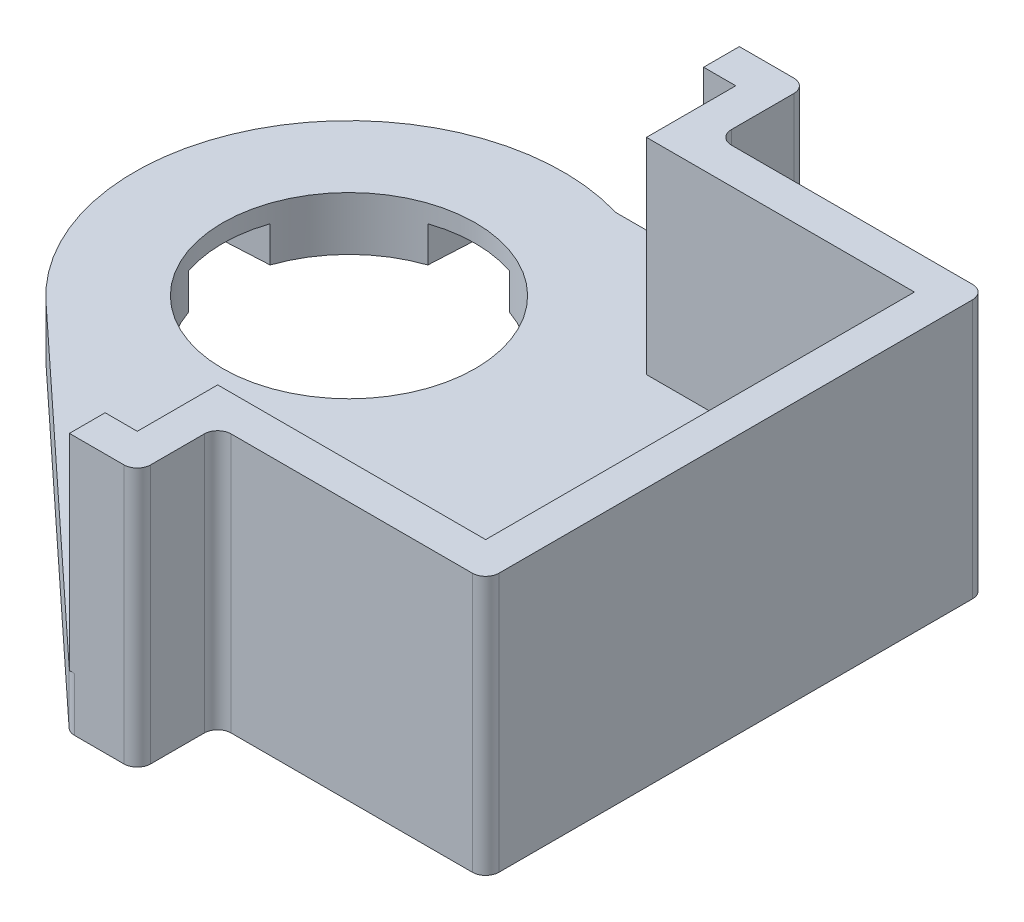
SolidWorks part; units mm, degrees
ref_plane "Front Plane" through (0, 0, 0) normal (0, 0, 1) x (1, 0, 0)
ref_plane "Top Plane" through (0, 0, 0) normal (0, 1, 0) x (1, 0, 0)
ref_plane "Right Plane" through (0, 0, 0) normal (1, 0, 0) x (0, 0, -1)
sketch "Sketch1" plane through (0, 0, 0) normal (0, 1, 0) x (1, 0, 0)
  line L0 (3.35, 28) -> (3.35, 23)
  line L9 (0, 0) -> (3.35, 0)
  line L10 (0, 0) -> (0, 23)
  line L11 (0, 23) -> (3.35, 23)
  line L12 (19.65, 0) -> (19.65, 23)
  line L14 (4.65, 0) -> (4.65, -5)
  line L15 (4.65, -5) -> (3.35, -5)
  line L16 (3.35, 0) -> (3.35, -5)
  line L17 (4.65, -5) -> (3.35, -5)
  line L18 (4.65, -5) -> (4.65, 28) construction
  line L19 (4.65, 28) -> (3.35, 28)
  line L20 (3.35, -5) -> (3.35, 28) construction
  line L21 (4.65, 28) -> (4.65, 23)
  line L22 (4.65, 0) -> (19.65, 0)
  line L23 (4.65, 23) -> (19.65, 23)
  line L24 (2.85, 28) -> (2.85, 23.5)
  line L25 (-0.5, 23.5) -> (2.85, 23.5)
  line L26 (-0.5, -0.5) -> (-0.5, 23.5)
  line L27 (-0.5, -0.5) -> (2.85, -0.5)
  line L28 (2.85, -0.5) -> (2.85, -5)
  line L29 (5.15, -0.5) -> (5.15, -5)
  line L30 (5.15, -0.5) -> (20.15, -0.5)
  line L31 (20.15, -0.5) -> (20.15, 23.5)
  line L32 (5.15, 23.5) -> (20.15, 23.5)
  line L33 (5.15, 28) -> (5.15, 23.5)
  line L34 (4.65, -4.5) -> (3.35, -4.5)
  line L35 (4.65, -4.5) -> (3.35, -4.5)
  line L37 (5.15, -5) -> (5.15, 28)
  line L38 (3.85, -5) -> (3.85, 28)
  line L39 (2.85, -5) -> (3.35, -5)
  line L40 (5.15, -5) -> (4.65, -5)
  line L41 (3.35, 28) -> (5.15, 28)
  line L42 (4.65, 28) -> (3.35, 28)
  line L43 (5.15, 28) -> (5.15, 28.5)
  line L46 (2.85, 28) -> (2.85, 28.5)
  line L47 (2.85, 28.5) -> (5.15, 28.5)
  line L48 (5.15, 28) -> (5.15, 28.5)
  dimension "D1" = 23
  dimension "D2" = 19.65
  dimension "D3" = 15
  dimension "D4" = 1.3
  dimension "D5" = 5
  dimension "D6" = 5
  dimension "D7" = 0.5
sketch "Sketch3" plane through (0, 0, 0) normal (0, 1, 0) x (1, 0, 0)
  line L1 (3.35, -5) -> (7.15, -5)
  line L2 (3.35, -5) -> (3.35, 28)
  line L3 (3.35, 28) -> (7.15, 28)
  line L4 (7.15, -5) -> (7.15, -2.5)
  line L5 (4.65, 28) -> (3.35, 28) construction
  line L6 (7.15, 25.5) -> (7.15, 28)
  line L7 (4.65, -5) -> (3.35, -5) construction
  line L8 (7.15, 25.5) -> (22.15, 25.5)
  line L10 (7.15, -2.5) -> (22.15, -2.5)
  line L11 (22.15, 25.5) -> (22.15, -2.5)
  line L12 (4.65, 23) -> (19.65, 23) construction
  line L13 (19.65, 0) -> (19.65, 23) construction
  line L14 (4.65, 0) -> (19.65, 0) construction
  line L15 (4.65, 0) -> (4.65, -5) construction
  point P20 (7.15, -3.75)
  dimension "D1" = 2.5
  dimension "D2" = 2.5
  dimension "D3" = 2.5
  dimension "D4" = 2.5
sketch "Sketch9" plane through (0, 0, 0) normal (0, 1, 0) x (1, 0, 0)
  line L0 (3.35, 28) -> (3.35, 23)
  line L9 (0, 0) -> (3.35, 0)
  line L10 (0, 0) -> (0, 23)
  line L11 (0, 23) -> (3.35, 23)
  line L12 (19.65, 0) -> (19.65, 23)
  line L14 (4.65, 0) -> (4.65, -4.5)
  line L15 (4.65, -5) -> (3.35, -5)
  line L16 (3.35, 0) -> (3.35, -4.5)
  line L17 (4.65, -5) -> (3.35, -5)
  line L18 (4.65, -4.5) -> (4.65, 28) construction
  line L19 (4.65, 28) -> (3.35, 28)
  line L20 (3.35, -4.5) -> (3.35, 28) construction
  line L21 (4.65, 28) -> (4.65, 23)
  line L22 (4.65, 0) -> (19.65, 0)
  line L23 (4.65, 23) -> (19.65, 23)
  line L24 (4.65, 28) -> (3.35, 28)
  line L25 (5.15, -5) -> (3.35, -5)
  line L26 (7.15, -5) -> (7.15, -6.25)
  line L27 (6.4, -7) -> (3.35, -7)
  line L28 (3.35, -5) -> (3.35, -7)
  line L29 (5.15, -0.5) -> (5.15, -5)
  line L30 (5.15, -0.5) -> (20.15, -0.5)
  line L31 (20.15, -0.5) -> (20.15, 23.5)
  line L32 (5.15, 23.5) -> (20.15, 23.5)
  line L33 (5.15, 28) -> (5.15, 23.5)
  line L34 (4.65, -4.5) -> (3.35, -4.5)
  line L35 (4.65, -4.5) -> (3.35, -4.5)
  line L36 (7.15, 28) -> (7.15, 26.25)
  line L37 (5.15, -5) -> (5.15, -0.5)
  line L38 (3.35, -5) -> (3.35, -7)
  line L40 (5.15, -5) -> (4.65, -5)
  line L41 (3.35, 28) -> (4.65, 28)
  line L42 (4.65, 28) -> (3.35, 28)
  line L43 (5.15, 28) -> (5.15, 28.5)
  line L47 (3.35, 30.5) -> (5.15, 30.5)
  line L48 (5.15, 28) -> (5.15, 28.5)
  line L49 (7.9, 25.5) -> (21.4, 25.5)
  line L50 (22.15, -1.75) -> (22.15, 24.75)
  line L51 (7.9, -2.5) -> (21.4, -2.5)
  line L52 (7.15, -3.25) -> (7.15, -5)
  line L53 (5.15, 23.5) -> (5.15, 28)
  line L54 (7.15, 28) -> (7.15, 29.75)
  line L55 (6.4, 30.5) -> (3.35, 30.5)
  line L57 (5.15, -5) -> (5.15, 28) construction
  line L58 (7.15, -2.5) -> (22.15, -2.5) construction
  line L60 (3.35, 30.5) -> (5.15, 30.5)
  line L61 (3.35, 30.5) -> (3.35, 28.5)
  line L62 (3.35, 28.5) -> (5.15, 28.5)
  line L64 (4.65, 0) -> (4.65, -5) construction
  line L65 (4.65, -5) -> (4.65, 28) construction
  line L66 (7.15, -2.5) -> (7.15, -5) construction
  line L67 (7.15, 28) -> (7.15, 25.5) construction
  line L68 (7.15, 25.5) -> (22.15, 25.5) construction
  line L69 (22.15, -2.5) -> (22.15, 25.5) construction
  arc A0 (7.9, -2.5) -> (7.15, -3.25) centre (7.9, -3.25) ccw
  arc A1 (7.15, 26.25) -> (7.9, 25.5) centre (7.9, 26.25) ccw
  arc A2 (7.15, 29.75) -> (6.4, 30.5) centre (6.4, 29.75) ccw
  arc A3 (21.4, 25.5) -> (22.15, 24.75) centre (21.4, 24.75) cw
  arc A4 (22.15, -1.75) -> (21.4, -2.5) centre (21.4, -1.75) cw
  arc A5 (7.15, -6.25) -> (6.4, -7) centre (6.4, -6.25) cw
  dimension "D10" = 0.75
  dimension "D1" = 23
  dimension "D2" = 19.65
  dimension "D3" = 15
  dimension "D4" = 1.3
  dimension "D5" = 5
  dimension "D6" = 5
  dimension "D7" = 0.5
  dimension "D8" = 2.5
  dimension "D9" = 2
  dimension "D11" = 0.5
extrude "Bracket" add sketch "Sketch9" along normal blind 11.5 contours L61 L62 L43 L33 L32 L31 L30 L29 L25 L15 L28 L27 L26 L52 L51 L50 L49 L36 L54 L55 L47 region at (4.9, 0, 5.4195)
sketch "Sketch12" plane through (0, 0, 0) normal (0, 1, 0) x (1, 0, 0)
  line L0 (3.1341, -6.7994) -> (-15.1691, 10.209)
  line L2 (-3.4667, 30.5) -> (6.4, 30.5)
  line L3 (7.15, 29.75) -> (7.15, 26.25)
  line L4 (7.9, 25.5) -> (21.4, 25.5)
  line L5 (22.15, 24.75) -> (22.15, -1.75)
  line L6 (21.4, -2.5) -> (7.9, -2.5)
  line L7 (7.15, -3.25) -> (7.15, -6.25)
  line L8 (6.4, -7) -> (3.6447, -7)
  arc A0 (-3.6746, 30.5294) -> (-15.1691, 10.209) centre (-7.0005, 18.9995) ccw
  arc A1 (3.1341, -6.7994) -> (3.6447, -7) centre (3.6447, -6.25) ccw
  arc A2 (7.15, -6.25) -> (6.4, -7) centre (6.4, -6.25) cw
  arc A3 (7.9, -2.5) -> (7.15, -3.25) centre (7.9, -3.25) ccw
  arc A4 (22.15, -1.75) -> (21.4, -2.5) centre (21.4, -1.75) cw
  arc A5 (21.4, 25.5) -> (22.15, 24.75) centre (21.4, 24.75) cw
  arc A6 (7.15, 26.25) -> (7.9, 25.5) centre (7.9, 26.25) ccw
  arc A7 (6.4, 30.5) -> (7.15, 29.75) centre (6.4, 29.75) cw
  arc A8 (-3.4667, 30.5) -> (-3.6746, 30.5294) centre (-3.4667, 31.25) cw
  point P17 (3.35, -7)
  point P22 (7.15, -2.5)
  point P25 (22.15, -2.5)
  point P28 (22.15, 25.5)
  point P31 (7.15, 25.5)
  point P36 (0, 0)
  dimension "D1" = 0.75
extrude "Boss-Extrude1" add sketch "Sketch12" against normal blind 3
sketch "Sketch15" plane through (0, 0, 0) normal (0, 1, 0) x (1, 0, 0)
  line L1 (-4.5, 21.5) -> (4.9995, 21.0005)
  line L2 (-7.0001, 21.5) -> (-7.0005, 30.9995)
  line L5 (-4.5, 21.5) -> (-9.5, 21.5)
  line L7 (-9.5, 21.5) -> (-9.0005, 30.9995)
  line L8 (-4.5, 21.5) -> (-5.0005, 30.9995)
  line L9 (-4.5, 16.5) -> (4.9995, 17.0005)
  line L10 (-4.5, 16.5) -> (-4.5, 21.5)
  line L11 (-4.5, 16.5) -> (-4.9995, 7.0005)
  line L12 (-9.5, 16.5) -> (-8.9995, 7.0005)
  line L13 (-9.5, 16.5) -> (-4.5, 16.5)
  line L14 (-9.5, 16.5) -> (-18.9995, 16.9995)
  line L15 (-9.5, 21.5) -> (-18.9995, 20.9995)
  line L16 (-9.5, 21.5) -> (-9.5, 16.5)
  circle A1 centre (-7, 19) radius 7.0711
  arc A6 (-3.6746, 30.5294) -> (-15.1691, 10.209) centre (-7.0005, 18.9995) ccw construction
  arc A7 (-9.0005, 30.9995) -> (-5.0005, 30.9995) centre (-7.0005, 30.9995) cw
  arc A8 (4.9995, 21.0005) -> (4.9995, 17.0005) centre (4.9995, 19.0005) cw
  arc A9 (-4.9995, 7.0005) -> (-8.9995, 7.0005) centre (-6.9995, 7.0005) cw
  arc A10 (-18.9995, 16.9995) -> (-18.9995, 20.9995) centre (-18.9995, 18.9995) cw
  point P0 (-7, 19)
  point P9 (-7, 19)
  point P12 (-7, 19)
  point P15 (-7, 19)
  point P18 (-7, 19)
  point P34 (-7, 19)
  dimension "D1" = 4
  dimension "D2" = 4
extrude "Cut-Extrude1" cut sketch "Sketch15" along normal blind 2 from surface contours A7 L7 A1 L8 | A10 L14 A1 L15 | A9 L11 A1 L12 | L9 A1 L1 L10 | A8 L1 A1 L9 | A1 | L9 A8 L1 L10 region at (-2.3114, 0, -19.0001) region at (3.1936, 0, -19.0004) region at (-7.0004, 0, -29.1936) region at (-6.9996, 0, -8.8064) region at (-17.1936, 0, -18.9996) starting at face at (7.1197, -3, -11.8189)
extrude "Cut-Extrude2" cut sketch "Sketch15<4>" against normal blind 2.5 contours L7 A1 L15 | L2 A1 L7 L5 | L8 A1 L2 L5 | L1 A1 L8 | L11 A1 L9 | L9 A1 L1 L10 | L5 L16 L13 L10 | L12 A1 L11 L13 | L15 A1 L14 L16 | L14 A1 L12 region at (-2.9514, 0, -23.0488) region at (-7, 0, -19) region at (-5.8229, 0, -23.6886) region at (-2.3114, 0, -19.0001) region at (-8.1774, 0, -23.6886) region at (-2.9512, 0, -14.9514) region at (-6.9999, 0, -14.3114) region at (-11.0488, 0, -23.0486) region at (-11.6886, 0, -18.9999) region at (-11.0486, 0, -14.9512)
sketch "Sketch15<4>" plane through (0, 0, 0) normal (0, 1, 0) x (1, 0, 0) same geometry as "Sketch15"
